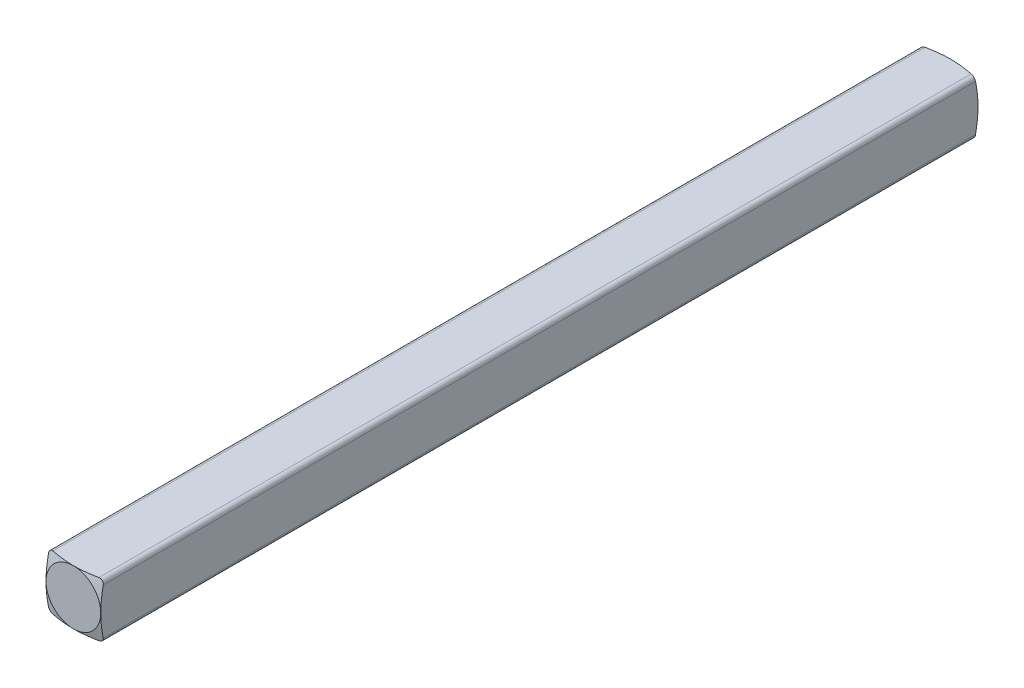
SolidWorks part; units mm, degrees
material "Plain Carbon Steel"
ref_plane "Front Plane" through (0, 0, 0) normal (0, 0, 1) x (1, 0, 0)
ref_plane "Top Plane" through (0, 0, 0) normal (0, 1, 0) x (1, 0, 0)
ref_plane "Right Plane" through (0, 0, 0) normal (1, 0, 0) x (0, 0, -1)
sketch "Sketch1" plane through (0, 0, 0) normal (0, 0, 1) x (1, 0, 0)
  line L0 (0.0501, 1.585) -> (0.0501, -1.585) construction
  line L1 (-1.5349, -1.585) -> (1.6351, -1.585)
  line L2 (-1.5349, -1.585) -> (-1.5349, 1.585)
  line L3 (-1.5349, 1.585) -> (1.6351, 1.585)
  line L4 (1.6351, -1.585) -> (1.6351, 1.585)
  line L5 (1.6351, 0) -> (-1.5349, 0) construction
  dimension "D1" = 3.17
  dimension "D2" = 3.17
  dimension "D3" = 1.6351
extrude "Extrude1" add sketch "Sketch1" along normal mid plane 50.8
sketch "Sketch4" plane through (0, 0, 0) normal (0, -1, 0) x (1, 0, 0)
  line L0 (1.6351, 25.4) -> (2.5551, 25.4)
  line L2 (2.5551, 25.4) -> (2.5551, 25.13)
  line L5 (0.0501, -25.4) -> (0.0501, 2.4929) construction
  line L6 (-1.5349, -25.4) -> (1.6351, -25.4) construction
  line L7 (1.6351, 11.0508) -> (1.6351, 10.1958) construction
  line L8 (2.5551, 25.13) -> (1.6351, 25.4)
  dimension "D1" = 0.27
  dimension "D2" = 0.9588
revolve "Cut-Revolve3" cut sketch "Sketch4" angle 360 about L5
mirror "Mirror2" about plane through (0, 0, 0) normal (0, 0, 1) of "Cut-Revolve3"
fillet "Fillet1" radius 0.25 4 edges at (1.6351, 1.585, 0) (1.6351, -1.585, 0) (-1.5349, -1.585, 0) (-1.5349, 1.585, 0)
ref_axis "Axis1" through (0.0501, 0, 35.6182) along (0, 0, -1)
ref_plane "Plane1" through (0, 0, -6.4) normal (0, 0, -1) x (-1, 0, 0)
ref_plane "Plane2" through (0, 0, 18.88) normal (0, 0, 1) x (1, 0, 0)
ref_plane "Plane3" through (0, 0, 9.4) normal (0, 0, -1) x (-1, 0, 0)
